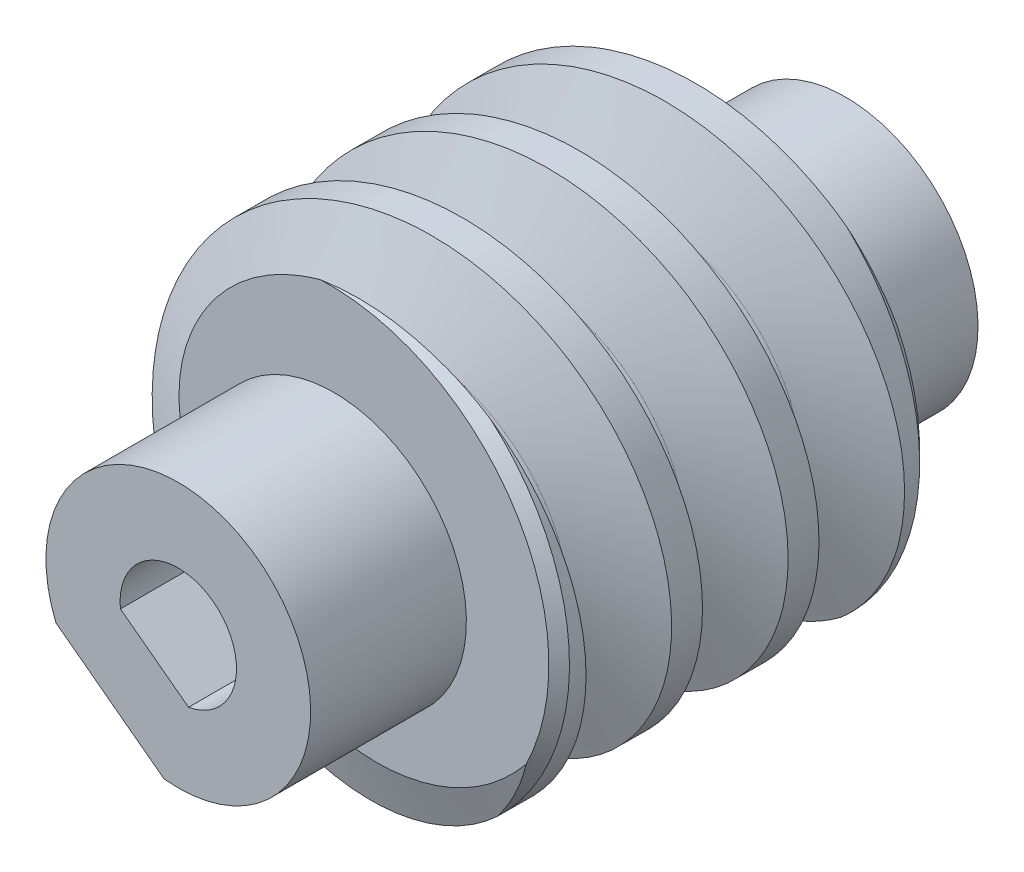
SolidWorks part; units mm, degrees
note: '?' marks a value the reader was unsure of.
ref_plane "Спереди" through (0, 0, 0) normal (0, 0, 1) x (1, 0, 0)
ref_plane "Сверху" through (0, 0, 0) normal (0, 1, 0) x (1, 0, 0)
ref_plane "Справа" through (0, 0, 0) normal (1, 0, 0) x (0, 0, -1)
ref_axis "Ось1" through (0, 0, 55) along (0, 0, -1)?
sketch "SketchRevolveWorm01" plane through (0, 0, 0) normal (1, 0, 0) x (0, 0, -1)
  line L0 (0, 0) -> (1, 0) construction
  line L1 (5, 0) -> (5, 5.922)
  line L2 (5, 5.922) -> (4.722, 6.2)
  line L3 (4.722, 6.2) -> (-4.722, 6.2)
  line L4 (-4.722, 6.2) -> (-5, 5.922)
  line L5 (-5, 5.922) -> (-5, 0)
  line L6 (-5, 0) -> (5, 0)
  dimension "ChamferX" = 0.278
  dimension "ChamferY" = 0.278
  dimension "OutsideDiameter" = 6.2
  dimension "WormLength" = 10
revolve "Worm01" add sketch "SketchRevolveWorm01" angle 360 about L0
ref_plane "HelixPlaneWorm01" through (0, 0, 9.4248) normal (0, 0, 1) x (1, 0, 0)
sketch "SketchHelixWorm01" plane through (0, 0, 9.4248) normal (0, 0, 1) x (1, 0, 0)
  circle A0 centre (0, 0) radius 5
  dimension "PitchDiameter" = 10
curve "GearHelixWorm01" pitch 3.1416 height 18.8496 turns 6
sketch "SketchToothWorm01" plane through (0, 0, 0) normal (0, 1, 0) x (1, 0, 0)
  line L0 (6.4426, -8.182) -> (4.1395, -9.0248)
  line L1 (3.9426, -9.3065) -> (3.9426, -9.5431)
  line L2 (4.1395, -9.8248) -> (6.4426, -10.6676)
  line L3 (6.4426, -10.6676) -> (6.4426, -8.182)
  arc A0 (4.1395, -9.0248) -> (3.9426, -9.3065) centre (4.2426, -9.3065) ccw
  arc A1 (3.9426, -9.5431) -> (4.1395, -9.8248) centre (4.2426, -9.5431) ccw
sweep "ToothCutWorm01" cut profiles "SketchToothWorm01" path "GearHelixWorm01"
sketch "BoreRevolveSketch" plane through (0, 0, 0) normal (1, 0, 0) x (0, 0, -1)
  line L0 (-5, 0) -> (5, 0)
  line L1 (5, 0) -> (5, 2.5)
  line L2 (5, 2.5) -> (-5, 2.5)
  line L3 (-5, 2.5) -> (-5, 0)
  dimension "TaperSide1" = 2.5
  dimension "TaperSide2" = 2.5
sketch "AuxiliarySketchWorm01" plane through (0, 0, 0) normal (0, 0, 1) x (1, 0, 0)
  circle A0 centre (0, 0) radius 5 construction
  dimension "PitchDiameter" = 10
sketch "Эскиз1" plane through (0, 0, 5) normal (0, 0, 1) x (1, 0, 0)
  line L2 (-1.4344, -0.2699) -> (0.4038, -1.6487)
  line L3 (-1.4344, -0.2699) -> (0.4038, -1.6487)
  arc A2 (0.4038, -1.6487) -> (-1.4344, -0.2699) centre (0.1267, -0.1033) ccw
  arc A3 (0.4038, -1.6487) -> (-1.4344, -0.2699) centre (0.1267, -0.1033) ccw
  dimension "D1" = 0.1
extrude "Вырез-Вытянуть1" cut sketch "Эскиз1" against normal through all contours A3 L3
sketch "Эскиз2" plane through (0, 0, -5) normal (0, 0, -1) x (-1, 0, 0)
  line L0 (1.4344, -0.2699) -> (-0.4038, -1.6487) construction
  line L1 (1.4344, -0.2699) -> (-0.4038, -1.6487)
  arc A0 (1.4344, -0.2699) -> (-0.4038, -1.6487) centre (-0.1267, -0.1033) ccw construction
  arc A1 (1.4344, -0.2699) -> (-0.4038, -1.6487) centre (-0.1267, -0.1033) ccw
extrude "Вытянуть-Тонкостенный1" add sketch "Эскиз2" along normal offset from surface 0.2 and the other way offset from surface (14.2 mm away) 0.2 thin thin type one direction wall 2
